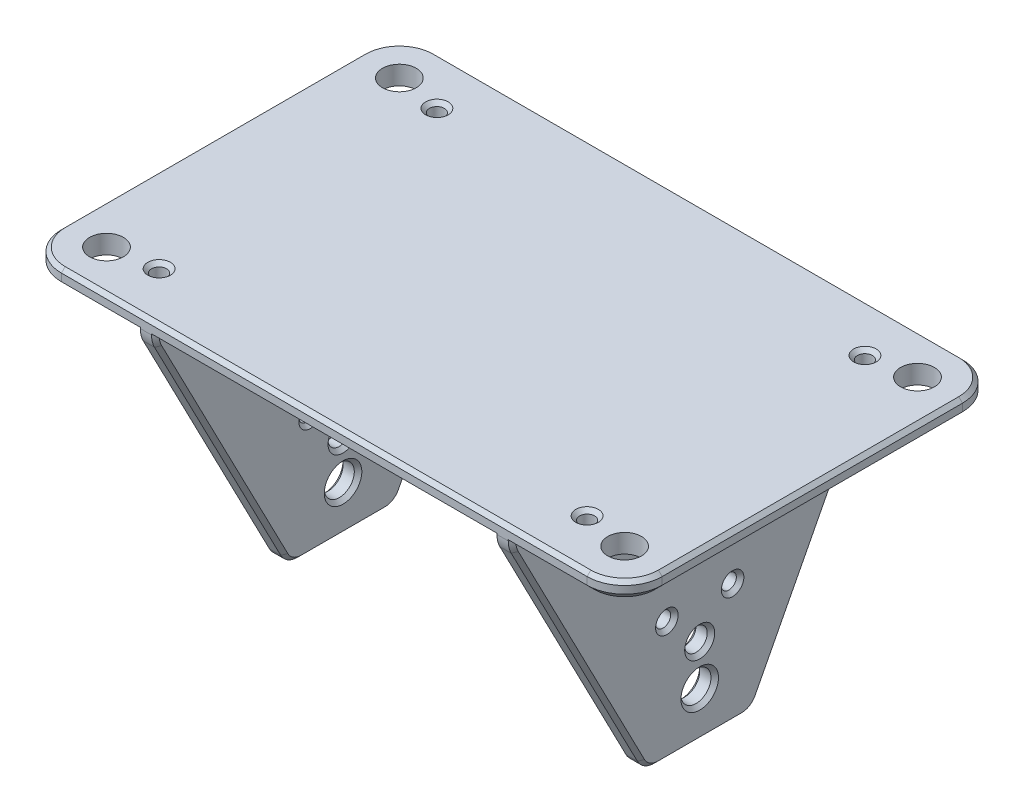
SolidWorks part; units mm, degrees
ref_plane "Front Plane" through (0, 0, 0) normal (0, 0, 1) x (1, 0, 0)
ref_plane "Top Plane" through (0, 0, 0) normal (0, 1, 0) x (1, 0, 0)
ref_plane "Right Plane" through (0, 0, 0) normal (1, 0, 0) x (0, 0, -1)
sketch "Sketch1" plane through (0, 0, 0) normal (0, 1, 0) x (1, 0, 0)
  line L1 (-80, -50) -> (80, -50)
  line L2 (-80, -50) -> (-80, 50)
  line L3 (-80, 50) -> (80, 50)
  line L4 (80, -50) -> (80, 50)
  line L5 (-80, -50) -> (80, 50) construction
  line L6 (-80, 50) -> (80, -50) construction
  point P0 (0, 0)
  dimension "D1" = 160
  dimension "D2" = 100
extrude "Boss-Extrude1" add sketch "Sketch1" against normal blind 5
sketch "Sketch2" plane through (0, 0, 0) normal (0, 1, 0) x (1, 0, 0)
  line L5 (-57, -37) -> (57, 37) construction
  line L6 (-57, 37) -> (57, -37) construction
  circle A0 centre (-57, 37) radius 2
  circle A1 centre (57, 37) radius 2
  circle A2 centre (57, -37) radius 2
  circle A3 centre (-57, -37) radius 2
  point P0 (0, 0)
  dimension "D3" = 4
  dimension "D1" = 114
  dimension "D2" = 74
extrude "Cut-Extrude1" cut sketch "Sketch2" against normal through all
sketch "Sketch3" plane through (0, 0, 0) normal (0, 1, 0) x (1, 0, 0)
  line L5 (-69, -39) -> (69, 39) construction
  line L6 (-69, 39) -> (69, -39) construction
  circle A0 centre (-69, 39) radius 4.5
  circle A1 centre (69, 39) radius 4.5
  circle A2 centre (-69, -39) radius 4.5
  circle A3 centre (69, -39) radius 4.5
  point P0 (0, 0)
  dimension "D1" = 138
  dimension "D2" = 78
extrude "Cut-Extrude2" cut sketch "Sketch3" against normal through all
sketch "Sketch4" plane through (-80, 0, 0) normal (-1, 0, 0) x (0, 0, 1)
  line L0 (-50, 0) -> (50, 0) construction
  line L1 (-14.2, 0) -> (14.2, 0)
  line L2 (-14.2, 0) -> (-14.2, -5)
  line L3 (-14.2, -74) -> (14.2, -74)
  line L4 (14.2, 0) -> (14.2, -5)
  line L5 (-14.2, -74) -> (-50, -5)
  line L6 (-50, -5) -> (50, -5)
  line L7 (50, -5) -> (14.2, -74)
  line M10 (-50, -5) -> (50, -5)
  dimension "D1" = 28.4
  dimension "D2" = 14.2
  dimension "D3" = 74
extrude "Boss-Extrude2" add sketch "Sketch4" against normal blind 5 from offset 30 contours L7 L5 L3 M10 offset against normal yes
ref_plane "Plane1" through (0, 0, 0) normal (-1, 0, 0) x (0, 0, 1)
mirror "Mirror1" about plane through (0, 0, 0) normal (-1, 0, 0) of "Boss-Extrude2"
sketch "Sketch6" plane through (-50, 0, 0) normal (-1, 0, 0) x (0, 0, 1)
  line L0 (0, 0) -> (0, -77.9378) construction
  line L1 (-50, 0) -> (50, 0) construction
  circle A0 centre (-8.75, -42) radius 2
  circle A1 centre (0, -51) radius 3
  circle A2 centre (0, -61.8) radius 4
  circle A3 centre (8.75, -42) radius 2
  dimension "D1" = 4
  dimension "D4" = 9
  dimension "D5" = 10.8
  dimension "D2" = 8.75
  dimension "D3" = 42
extrude "Cut-Extrude3" cut sketch "Sketch6" against normal through all
fillet "Fillet3" radius 5 4 edges at (-47.5, -74, -14.2) (-47.5, -74, 14.2) (47.5, -74, -14.2) (47.5, -74, 14.2)
fillet "Fillet9" radius 10 4 edges at (80, -2.5, 50) (80, -2.5, -50) (-80, -2.5, -50) (-80, -2.5, 50)
chamfer "Chamfer2" distance 2 angle 45 12 edges at (60, -5, 50) (0, -5, 50) (80, -5, 0) (60, -5, -50) (0, -5, -50) (-60, -5, -50) (-80, -5, 0) (-60, -5, 50) (77.0711, -5, 47.0711) (77.0711, -5, -47.0711) (-77.0711, -5, -47.0711) (-77.0711, -5, 47.0711)
fillet "Fillet8" radius 7 4 edges at (47.5, -5, 50) (-47.5, -5, 50) (47.5, -5, -50) (-47.5, -5, -50)
chamfer "Chamfer3" distance 1 angle 45 52 edges at (45, -61.8, -4) (45, -51, -3) (45, -42, 6.75) (45, -42, -10.75) (-50, -61.8, 4) (-50, -51, 3) (-50, -42, 6.75) (-50, -42, -6.75) (-45, -61.8, 4) (-45, -51, 3) (-45, -42, -6.75) (-45, -42, 10.75) (50, -61.8, -4) (50, -51, -3) (50, -42, 6.75) (50, -42, -10.75) (-45, -3.1461, -50) (-45, -4.9513, -49.8005) (-45, -38.9093, -32.4065) (-45, -73.2728, -13.758) (-45, -3.1461, 50) (-45, -74, 0) (-45, -4.9513, 49.8005) (-45, -73.2728, 13.758) (-45, -38.9093, 32.4065) (45, -3.1461, -50) (45, -4.9513, -49.8005) (45, -38.9093, -32.4065) (45, -73.2728, -13.758) (45, -3.1461, 50) (45, -74, 0) (45, -4.9513, 49.8005) (45, -73.2728, 13.758) (45, -38.9093, 32.4065) (50, -3.1461, -50) (50, -4.9513, -49.8005) (50, -38.9093, -32.4065) (50, -73.2728, -13.758) (50, -3.1461, 50) (50, -74, 0) (50, -4.9513, 49.8005) (50, -73.2728, 13.758) (50, -38.9093, 32.4065) (-50, -3.1461, -50) (-50, -4.9513, -49.8005) (-50, -38.9093, -32.4065) (-50, -73.2728, -13.758) (-50, -3.1461, 50) (-50, -74, 0) (-50, -4.9513, 49.8005) (-50, -73.2728, 13.758) (-50, -38.9093, 32.4065)
chamfer "Chamfer4" distance 1 angle 45 8 edges at (0, 0, 50) (-80, 0, 0) (0, 0, -50) (80, 0, 0) (-77.0711, 0, 47.0711) (-77.0711, 0, -47.0711) (77.0711, 0, -47.0711) (77.0711, 0, 47.0711)
chamfer "Chamfer5" distance 1 angle 45 8 edges at (57, 0, -35) (57, 0, 39) (57, -5, 39) (57, -5, -35) (-57, -5, -35) (-57, -5, 39) (-57, 0, 39) (-57, 0, -35)
